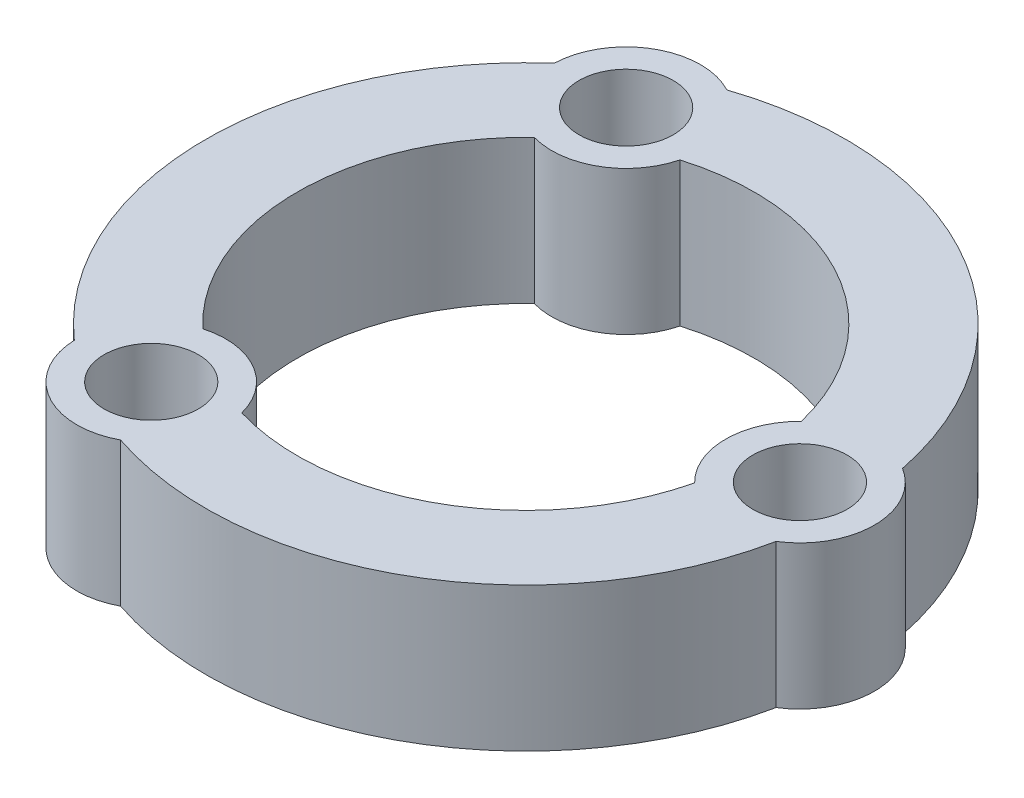
SolidWorks part; units mm, degrees
material "ABS"
ref_plane "Front Plane" through (0, 0, 0) normal (0, 0, 1) x (1, 0, 0)
ref_plane "Top Plane" through (0, 0, 0) normal (0, 1, 0) x (1, 0, 0)
ref_plane "Right Plane" through (0, 0, 0) normal (1, 0, 0) x (0, 0, -1)
sketch "Sketch1" plane through (0, 0, 0) normal (0, 1, 0) x (1, 0, 0)
  arc A0 (21.7892, 4.3921) -> (-7.0909, 21.0661) centre (0, 0) ccw
  arc A1 (15.4392, 3.7047) -> (15.4392, -3.7047) centre (19.0525, 0) ccw
  circle A2 centre (-9.5263, -16.4999) radius 3.175 construction
  circle A3 centre (-9.5262, 16.4999) radius 3.175 construction
  circle A4 centre (19.0525, 0) radius 3.175 construction
  circle A5 centre (-9.5262, 16.4999) radius 3.175
  circle A6 centre (19.0525, 0) radius 3.175
  circle A7 centre (-9.5263, -16.4999) radius 3.175
  arc A8 (-4.5112, -15.2231) -> (-10.928, -11.5184) centre (-9.5263, -16.4999) ccw
  arc A9 (21.7892, -4.3921) -> (21.7892, 4.3921) centre (19.0525, 0) ccw
  arc A10 (-7.0909, 21.0661) -> (-14.6983, 16.674) centre (-9.5262, 16.4999) ccw
  arc A11 (15.4392, 3.7047) -> (-4.5112, 15.2231) centre (0, 0) ccw
  circle A12 centre (19.0525, 0) radius 5.175 construction
  arc A13 (-10.928, 11.5184) -> (-4.5112, 15.2231) centre (-9.5262, 16.4999) ccw
  circle A14 centre (-9.5262, 16.4999) radius 5.175 construction
  arc A15 (-10.928, 11.5184) -> (-10.928, -11.5184) centre (0, 0) ccw
  arc A16 (-14.6983, 16.674) -> (-14.6983, -16.674) centre (0, 0) ccw
  arc A17 (-4.5112, -15.2231) -> (15.4392, -3.7047) centre (0, 0) ccw
  arc A18 (-7.0909, -21.0661) -> (21.7892, -4.3921) centre (0, 0) ccw
  circle A19 centre (-9.5263, -16.4999) radius 5.175 construction
  arc A20 (-14.6983, -16.674) -> (-7.0909, -21.0661) centre (-9.5263, -16.4999) ccw
  point P1 (30.1365, 0)
  point P20 (-4.9245, 20.2425)
  point P29 (-4.9245, -20.2425)
  dimension "D1" = 2
  dimension "D3" = 6.35
  dimension "D2" = 19.0525
extrude "Boss-Extrude1" add sketch "Sketch1" along normal blind 10 contours A7 | A5 | A6 | A16 A20 A18 A9 A0 A10 A5 A6 A7 A17 A8 A15 A13 A11 A1 region at (23.5845, 0, 0) region at (-9.5262, 0, -16.4999) region at (19.0525, 0, 0) region at (-9.5262, 0, 16.4999)
sketch "Sketch3" plane through (0, 10, 0) normal (0, 1, 0) x (1, 0, 0)
  circle A1 centre (19.0525, 0) radius 3.275
  arc A3 (15.4392, 3.7047) -> (15.4392, -3.7047) centre (19.0525, 0) ccw construction
  dimension "D1" = 6.55
extrude "Cut-Extrude1" cut sketch "Sketch3" against normal blind 7.5
pattern_circular "CirPattern1" count 3 every 120 about axis through (0, 10, 0) along (0, 1, 0) of "Cut-Extrude1"
